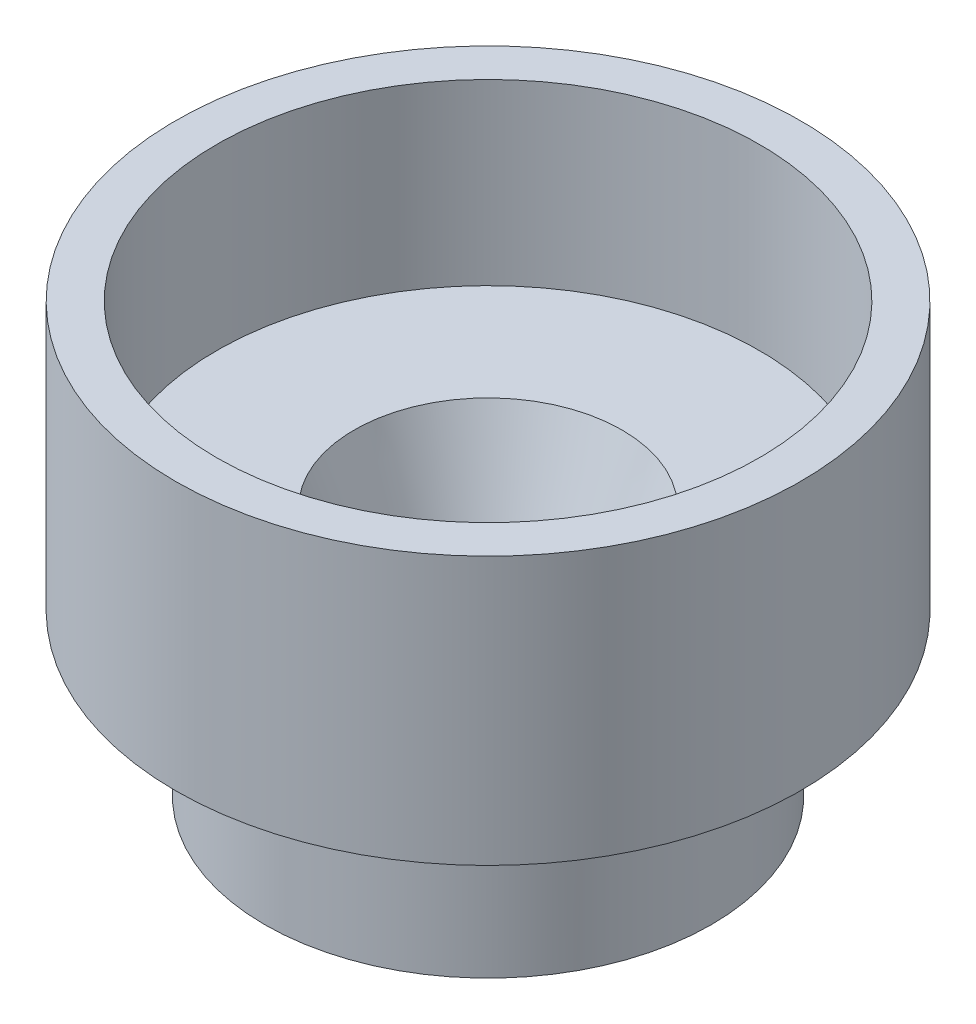
SolidWorks part; units mm, degrees
ref_plane "Front Plane" through (0, 0, 0) normal (0, 0, 1) x (1, 0, 0)
ref_plane "Top Plane" through (0, 0, 0) normal (0, 1, 0) x (1, 0, 0)
ref_plane "Right Plane" through (0, 0, 0) normal (1, 0, 0) x (0, 0, -1)
sketch "Sketch1" plane through (0, 0, 0) normal (0, 1, 0) x (1, 0, 0)
  circle A0 centre (0, 0) radius 7.6
  circle A1 centre (0, 0) radius 8.75
  dimension "D1" = 15.2
  dimension "D2" = 17.5
extrude "Boss-Extrude1" add sketch "Sketch1" along normal blind 7.5
extrude "Boss-Extrude2" add sketch "Sketch1<2>" along normal blind 2.5 contours A0 region at (0, 0, 0)
sketch "Sketch1<2>" plane through (0, 0, 0) normal (0, 1, 0) x (1, 0, 0) same geometry as "Sketch1"
sketch "Sketch2" plane through (0, 0, 0) normal (0, -1, 0) x (1, 0, 0)
  circle A0 centre (0, 0) radius 3.75
  circle A1 centre (0, 0) radius 6.25
  dimension "D1" = 7.5
  dimension "D2" = 12.5
extrude "Boss-Extrude3" add sketch "Sketch2" along normal blind 4.5 contours A1 | A0
sketch "Sketch3" plane through (0, 0, 0) normal (0, -1, 0) x (1, 0, 0)
  circle A1 centre (0, 0) radius 3.75
  circle A2 centre (0, 0) radius 3.75
  dimension "D1" = 0
extrude "Cut-Extrude1" cut sketch "Sketch3" against normal blind 4.5
sketch "Sketch4" plane through (0, 0, 0) normal (0, 0, 1) x (1, 0, 0)
  line L0 (3.75, 2.5) -> (-3.75, 2.5) construction
  line L1 (3.75, 2.5) -> (-3.75, 2.5)
  line L2 (3.75, 2.5) -> (2.25, -1.5)
  line L3 (2.25, -1.5) -> (3.75, -1.5)
  line L4 (3.75, -1.5) -> (3.75, 2.5)
  line L5 (0, 6.4886) -> (0, -3.7414) construction
  dimension "D1" = 4
  dimension "D2" = 1.5
revolve "Revolve1" add sketch "Sketch4" angle 360 about L5 region at (3.25, -0.1667, 0)
